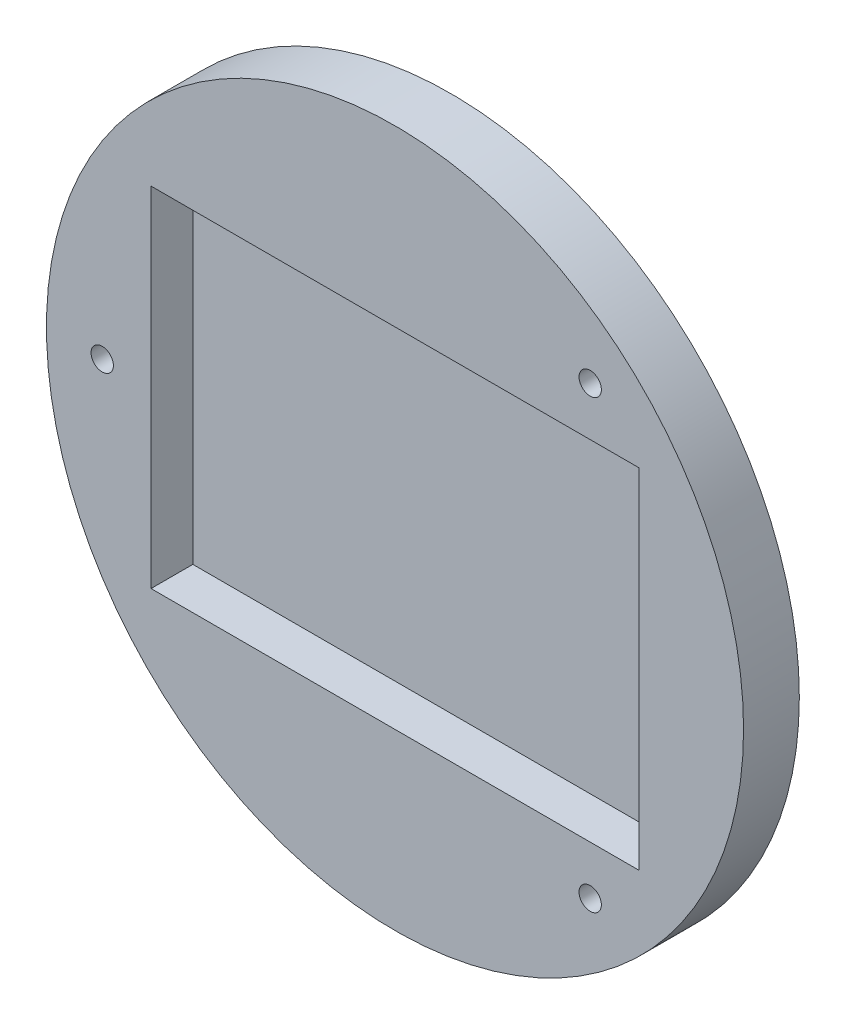
SolidWorks part; units mm, degrees
material "Nylon 101"
ref_plane "Front Plane" through (0, 0, 0) normal (0, 0, 1) x (1, 0, 0)
ref_plane "Top Plane" through (0, 0, 0) normal (0, 1, 0) x (1, 0, 0)
ref_plane "Right Plane" through (0, 0, 0) normal (1, 0, 0) x (0, 0, -1)
sketch "Sketch1" plane through (0, 0, 0) normal (0, 0, 1) x (1, 0, 0)
  line L1 (-18.5, 13.5) -> (18.5, 13.5)
  line L2 (-18.5, 13.5) -> (-18.5, -13.5)
  line L3 (-18.5, -13.5) -> (18.5, -13.5)
  line L4 (18.5, 13.5) -> (18.5, -13.5)
  line L5 (-18.5, 13.5) -> (18.5, -13.5) construction
  line L6 (-18.5, -13.5) -> (18.5, 13.5) construction
  line L7 (-17.5, 12.5) -> (17.5, 12.5)
  line L8 (-17.5, 12.5) -> (-17.5, -12.5)
  line L9 (-17.5, -12.5) -> (17.5, -12.5)
  line L10 (17.5, 12.5) -> (17.5, -12.5)
  line L11 (-17.5, 12.5) -> (17.5, -12.5) construction
  line L12 (-17.5, -12.5) -> (17.5, 12.5) construction
  circle A0 centre (0, 0) radius 25
  point P2 (0, 0)
  point P4 (0, 0)
  point P9 (0, 0)
  dimension "D1" = 50
  dimension "D2" = 27
  dimension "D3" = 37
  dimension "D4" = 1
  dimension "D5" = 1
extrude "Boss-Extrude1" add sketch "Sketch1" along normal blind 4 contours A0 L1 L4 L3 L2 | L4 L1 L2 L3 L7 L10 L9 L8 region at (0, 13.042, 0) region at (-24.2929, 0, 0)
extrude "Boss-Extrude2" add sketch "Sketch1<3>" along normal blind 1 contours L10 L7 L8 L9 region at (0, 0, 0)
sketch "Sketch1<3>" plane through (0, 0, 0) normal (0, 0, 1) x (1, 0, 0) same geometry as "Sketch1"
sketch "Sketch2" plane through (0, 0, 0) normal (0, 1, 0) x (1, 0, 0)
  line L4 (0, 15) -> (0, -15) construction
  line L5 (0, 6.5) -> (0, 0)
  line L6 (0, 0) -> (-6.5, 0)
  arc A1 (0, 6.5) -> (-6.5, 0) centre (0, 0) ccw
  point P2 (0, 0)
  dimension "D1" = 13
  dimension "D4" = 30
revolve "Revolve1" add sketch "Sketch2" angle 360 about L4
hole_wizard "M2x0.4 Tapped Hole1" positions "Sketch3" profile "Sketch4" tap size "M2x0.4" standard "ANSI Metric" end condition through all
sketch "Sketch3" plane through (0, 0, 4) normal (0, 0, 1) x (1, 0, 0)
  line L0 (-17.5, 12.5) -> (-17.5, -12.5) construction
  line L1 (-17.5, -12.5) -> (17.5, -12.5) construction
  line L2 (-17.5, 12.5) -> (17.5, 12.5) construction
  line L3 (17.5, 12.5) -> (17.5, -12.5) construction
  point P0 (-21, 0)
  point P2 (14, -16)
  point P4 (14, 16)
  point P15 (0, 0)
  point P16 (0, 0)
  dimension "D1" = 3.5
  dimension "D2" = 3.5
  dimension "D3" = 3.5
  dimension "D4" = 3.5
sketch "Sketch4" plane through (-21, 0, 4) normal (1, 0, 0) x (0, -1, 0)
  line L0 (0, 0) -> (0, 10.5)
  line L1 (0, 10.5) -> (0.8, 10.5)
  line L2 (0.8, 10.5) -> (0.8, 0)
  line L5 (0.8, 0) -> (0, 0)
  line L11 (0, -6.35) -> (0, 107.95) construction
  dimension "Thru Tap Drill Dia." = 1.6
  dimension "Thru Tap Drill Depth" = 10.5
cosmetic thread "Hole Thread1" parameters "D2"=2
cosmetic thread "Hole Thread2" parameters "D2"=2
cosmetic thread "Hole Thread3" parameters "D2"=2
